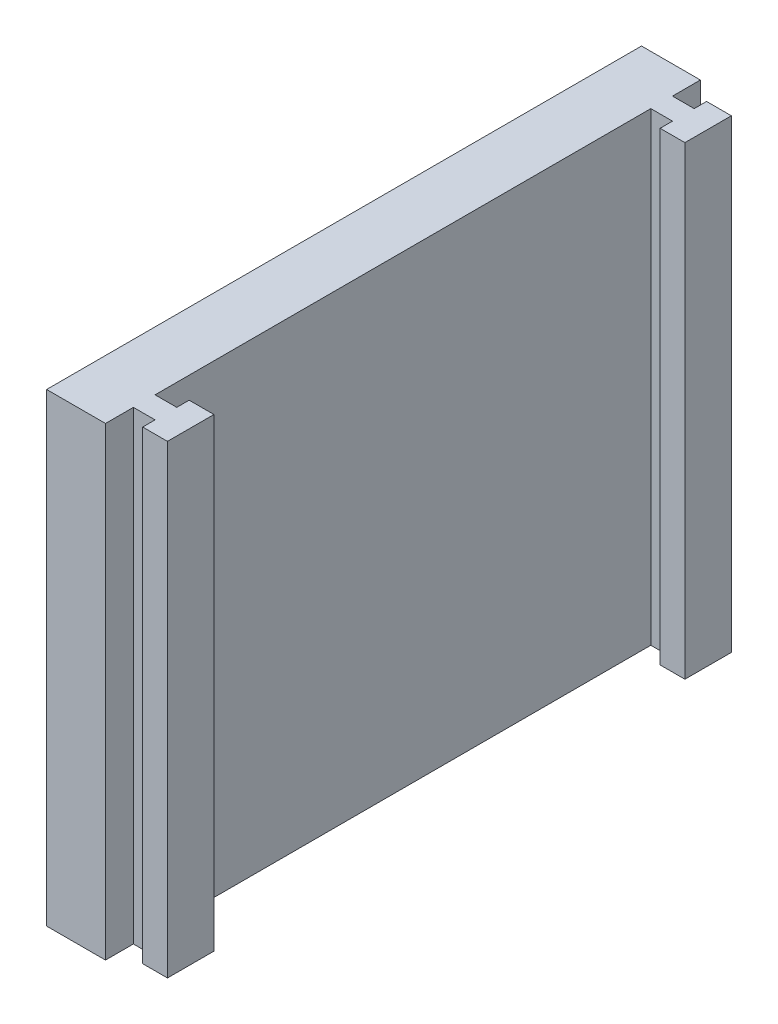
SolidWorks part; units mm, degrees
ref_plane "Piano frontale" through (0, 0, 0) normal (0, 0, 1) x (1, 0, 0)
ref_plane "Piano superiore" through (0, 0, 0) normal (0, 1, 0) x (1, 0, 0)
ref_plane "Piano destro" through (0, 0, 0) normal (1, 0, 0) x (0, 0, -1)
sketch "Schizzo2" plane through (0, 0, 0) normal (0, 1, 0) x (1, 0, 0)
  line L0 (19, 96) -> (19, 87)
  line L5 (19, 87) -> (26, 87)
  line L6 (19, 0) -> (0, 0)
  line L8 (19, 96) -> (0, 96)
  line L9 (0, 0) -> (0, 96)
  line L10 (26, 87) -> (26, 91)
  line L11 (26, 91) -> (34, 91)
  line L12 (26, 76) -> (26, 80)
  line L13 (34, 91) -> (34, 76)
  line L14 (26, 80) -> (19, 80)
  line L15 (19, 80) -> (19, 0)
  line L21 (34, 76) -> (26, 76)
  point P1 (0, 0)
  point P3 (0, 0)
  point P6 (0, 0)
  point P12 (0, 0)
  point P14 (0, 0)
  point P19 (0, 0)
  point P21 (34, 83.5)
  point P22 (-306.4741, 35.591)
  dimension "D1" = 7
  dimension "D2" = 8
  dimension "D3" = 34
  dimension "D4" = 19
  dimension "D5" = 0
  dimension "D6" = 0
  dimension "D7" = 15
  dimension "D8" = 12.5
  dimension "D9" = 5
  dimension "D10" = 4
  dimension "D11" = 4
  dimension "D12" = 9
  dimension "D13" = 96
  dimension "D15" = 80
extrude "Estrusione-Estrusione1" add sketch "Schizzo2" along normal blind 150
sketch "Schizzo3" plane through (0, 0, 0) normal (0, -1, 0) x (1, 0, 0)
  line L3 (9.7839, -91) -> (5, -91)
  line L4 (9.7839, -76) -> (5, -76)
  line L5 (5, -91) -> (5, -76)
  line L6 (0, -96) -> (0, 0) construction
  line L8 (19, -96) -> (0, -96) construction
  arc A0 (9.7839, -76) -> (9.7839, -91) centre (7, -83.5) cw
  point P6 (15, -83.5)
  dimension "D3" = 15
  dimension "D5" = 8
  dimension "D1" = 5
  dimension "D2" = 5
  dimension "D4" = 10
  dimension "D6" = 4.7839
extrude "Taglio-Estrusione1" cut sketch "Schizzo3" against normal blind 30
mirror "Specchia2" about plane through (19, 150, 0) normal (0, 0, -1) of bodies 103
